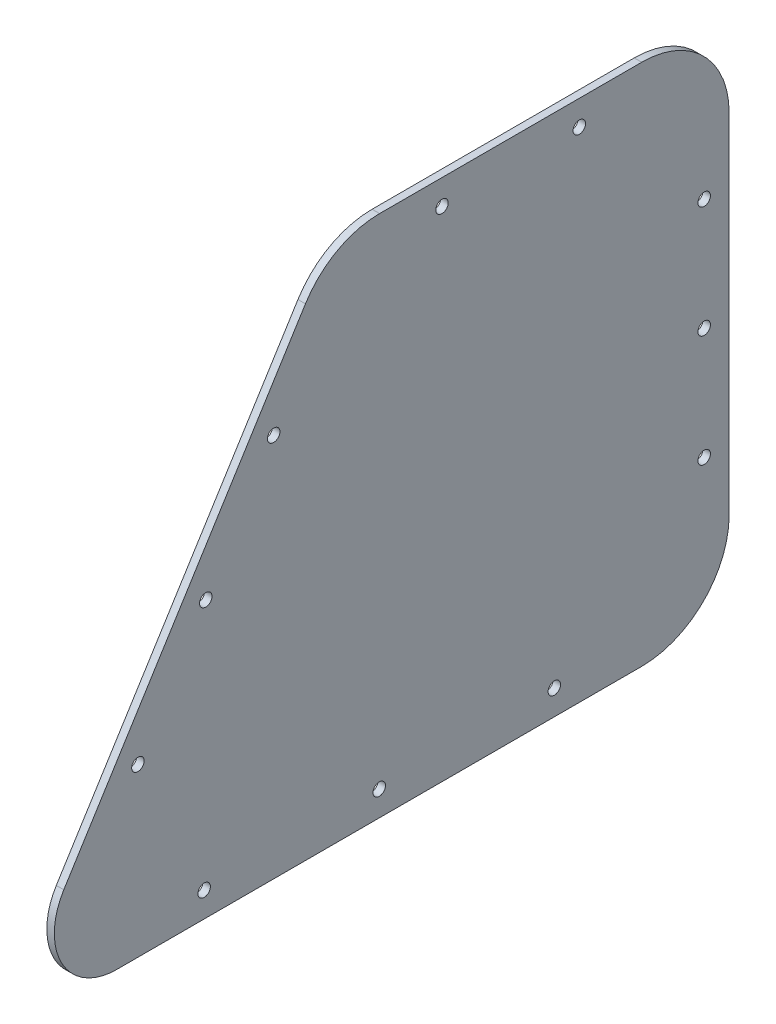
SolidWorks part; units mm, degrees
material "Acrylic (Medium-high impact)"
ref_plane "Front Plane" through (0, 0, 0) normal (0, 0, 1) x (1, 0, 0)
ref_plane "Top Plane" through (0, 0, 0) normal (0, 1, 0) x (1, 0, 0)
ref_plane "Right Plane" through (0, 0, 0) normal (1, 0, 0) x (0, 0, -1)
sketch "Sketch1" plane through (0, 0, 0) normal (1, 0, 0) x (0, 0, -1)
  line L0 (0, -1000) -> (0, 49000) construction
  line L1 (-1000, 0) -> (49000, 0) construction
  line L6 (-105.1013, 0) -> (105.1013, 0) construction
  line L7 (125.1013, 20) -> (125.1013, 159.5) construction
  line L8 (0.1286, 179.5) -> (105.1013, 179.5) construction
  line L9 (-16.8313, 170.1) -> (-113.5813, 15.3) construction
  line L10 (-105.1013, -15) -> (105.1013, -15)
  line L11 (140.1013, 20) -> (140.1013, 159.5)
  line L12 (0.1286, 194.5) -> (105.1013, 194.5)
  line L13 (-29.5513, 178.05) -> (-126.3013, 23.25)
  arc A4 (-113.5813, 15.3) -> (-105.1013, 0) centre (-105.1013, 10) ccw construction
  arc A5 (105.1013, 0) -> (125.1013, 20) centre (105.1013, 20) ccw construction
  arc A6 (125.1013, 159.5) -> (105.1013, 179.5) centre (105.1013, 159.5) ccw construction
  arc A7 (0.1286, 179.5) -> (-16.8313, 170.1) centre (0.1286, 159.5) ccw construction
  arc A8 (105.1013, -15) -> (140.1013, 20) centre (105.1013, 20) ccw
  arc A9 (140.1013, 159.5) -> (105.1013, 194.5) centre (105.1013, 159.5) ccw
  arc A10 (0.1286, 194.5) -> (-29.5513, 178.05) centre (0.1286, 159.5) ccw
  arc A11 (-126.3013, 23.25) -> (-105.1013, -15) centre (-105.1013, 10) ccw
  point P4 (0, 0)
  dimension "D2" = 20
  dimension "D3" = 10
  dimension "D1" = 139.5
  dimension "D4" = 104.9727
  dimension "D5" = 182.5475
  dimension "D6" = 105.1013
  dimension "D7" = 40
  dimension "D8" = 125.1013
  dimension "D9" = 179.5
  dimension "D10" = 10
  dimension "D11" = 57.995
  dimension "D12" = 15
extrude "Boss-Extrude1" add sketch "Sketch1" along normal blind 3
sketch "Sketch2" plane through (3, 0, 0) normal (1, 0, 0) x (0, 0, -1)
  line L38 (-105.1013, -5) -> (105.1013, -5)
  line L40 (130.1013, 20) -> (130.1013, 159.5)
  line L42 (105.1013, 184.5) -> (0.1286, 184.5)
  line L44 (-21.0713, 172.75) -> (-117.8213, 17.95)
  line L46 (-105.1013, -5) -> (105.1013, -5) construction
  line L47 (130.1013, 20) -> (130.1013, 159.5) construction
  line L48 (105.1013, 184.5) -> (0.1286, 184.5) construction
  line L49 (-21.0713, 172.75) -> (-117.8213, 17.95) construction
  circle A32 centre (80.1013, 184.5) radius 2.5
  circle A33 centre (25.1286, 184.5) radius 2.5
  circle A34 centre (130.1013, 134.5) radius 2.5
  circle A35 centre (130.1013, 89.75) radius 2.5
  arc A40 (-117.8213, 17.95) -> (-105.1013, -5) centre (-105.1013, 10) ccw
  arc A42 (105.1013, -5) -> (130.1013, 20) centre (105.1013, 20) ccw
  circle A44 centre (130.1013, 45) radius 2.5
  circle A45 centre (70.1013, -5) radius 2.5
  circle A46 centre (0, -5) radius 2.5
  circle A47 centre (-70.1013, -5) radius 2.5
  circle A48 centre (-96.6213, 51.8699) radius 2.5
  circle A49 centre (-69.4463, 95.35) radius 2.5
  circle A50 centre (-42.2713, 138.83) radius 2.5
  arc A51 (130.1013, 159.5) -> (105.1013, 184.5) centre (105.1013, 159.5) ccw
  arc A53 (0.1286, 184.5) -> (-21.0713, 172.75) centre (0.1286, 159.5) ccw
  arc A55 (-117.8213, 17.95) -> (-105.1013, -5) centre (-105.1013, 10) ccw construction
  arc A56 (105.1013, -5) -> (130.1013, 20) centre (105.1013, 20) ccw construction
  arc A57 (130.1013, 159.5) -> (105.1013, 184.5) centre (105.1013, 159.5) ccw construction
  arc A58 (0.1286, 184.5) -> (-21.0713, 172.75) centre (0.1286, 159.5) ccw construction
  point P1 (0, 0)
  point P2 (0, 0)
  point P3 (133.1197, 100.9032)
  point P4 (0, 0)
  point P6 (0, 0)
  point P7 (0, 0)
  point P8 (0, 0)
  point P9 (0, 0)
  point P11 (0, 0)
  point P12 (0, 0)
  dimension "D4" = 25
  dimension "D6" = 25
  dimension "D7" = 35
  dimension "D8" = 35
  dimension "D9" = 40
  dimension "D10" = 40
  dimension "D2" = 5
  dimension "D5" = 25
  dimension "D3" = 25
  dimension "D1" = 10
extrude "Cut-Extrude1" cut sketch "Sketch2" against normal up to next
